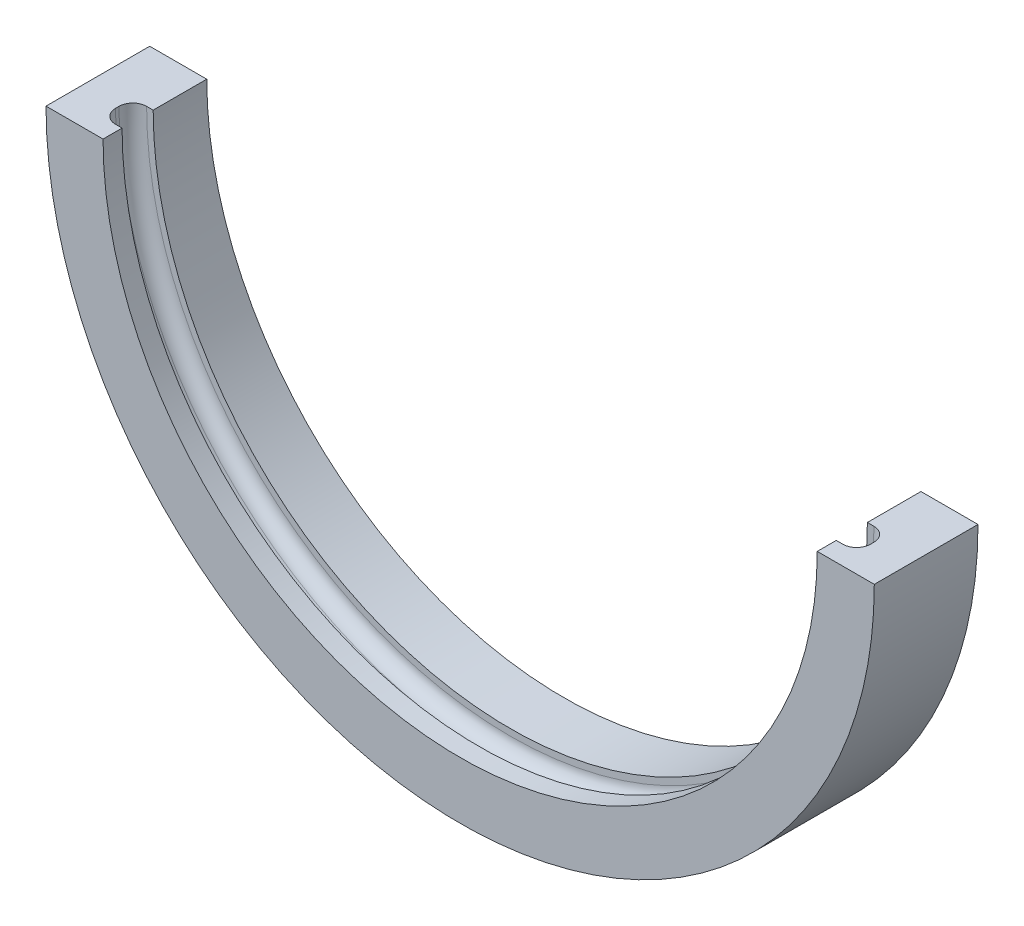
SolidWorks part; units mm, degrees
ref_plane "Front Plane" through (0, 0, 0) normal (0, 0, 1) x (1, 0, 0)
ref_plane "Top Plane" through (0, 0, 0) normal (0, 1, 0) x (1, 0, 0)
ref_plane "Right Plane" through (0, 0, 0) normal (1, 0, 0) x (0, 0, -1)
sketch "Sketch1" plane through (0, 0, 0) normal (0, 0, 1) x (1, 0, 0)
  line L0 (-69.342, 76.073) -> (-76.073, 76.073)
  line L1 (69.342, 76.073) -> (76.073, 76.073)
  circle A0 centre (0, 76.073) radius 76.073
  circle A1 centre (0, 76.073) radius 69.342
  dimension "D1" = 152.146
  dimension "D2" = 138.684
extrude "Boss-Extrude1" add sketch "Sketch1" along normal blind 5.715 contours A1 L0 A0 L1 region at (0, 5.03, 0)
sketch "Sketch3" plane through (0, 0, 5.715) normal (0, 0, 1) x (1, 0, 0)
  line L0 (-65.5955, 76.073) -> (-76.073, 76.073)
  line L1 (65.5955, 76.073) -> (76.073, 76.073)
  circle A0 centre (0, 76.073) radius 76.073
  circle A1 centre (0, 76.073) radius 65.5955
  arc M3 (69.342, 76.073) -> (-69.342, 76.073) centre (0, 76.073) cw
  line M4 (-69.342, 76.073) -> (-76.073, 76.073)
  arc M5 (-76.073, 76.073) -> (76.073, 76.073) centre (0, 76.073) ccw
  line M6 (76.073, 76.073) -> (69.342, 76.073)
  dimension "D1" = 131.191
extrude "Boss-Extrude2" add sketch "Sketch3" along normal blind 3.4925 contours A1 L0 L1 M3 | M6 M3 M4 M5 region at (0, 8.927, 5.715) region at (0, 5.03, 5.715)
sketch "Sketch4" plane through (0, 0, 0) normal (0, 0, -1) x (-1, 0, 0)
  line L0 (-65.5955, 76.073) -> (-76.073, 76.073)
  line L1 (65.5955, 76.073) -> (76.073, 76.073)
  circle A0 centre (0, 76.073) radius 76.073
  circle A1 centre (0, 76.073) radius 65.5955
  arc M3 (69.342, 76.073) -> (-69.342, 76.073) centre (0, 76.073) cw
  line M4 (-69.342, 76.073) -> (-76.073, 76.073)
  arc M5 (-76.073, 76.073) -> (76.073, 76.073) centre (0, 76.073) ccw
  line M6 (76.073, 76.073) -> (69.342, 76.073)
extrude "Boss-Extrude3" add sketch "Sketch4" along normal blind 9.8425 contours A1 L0 L1 M3 | M6 M3 M4 M5 region at (0, 8.927, 0) region at (0, 5.03, 0)
fillet "Fillet1" radius 2.54 2 edges at (0, 6.731, 5.715) (0, 6.731, 0)
sketch "Sketch5" plane through (0, 0, 0) normal (0, 1, 0) x (1, 0, 0)
  line L0 (64.2819, -2.8575) -> (-64.2819, -2.8575) construction
  circle A0 centre (0, -2.8575) radius 1.524
  dimension "D1" = 3.048
extrude "Cut-Extrude1" cut sketch "Sketch5" along normal blind 6.35
